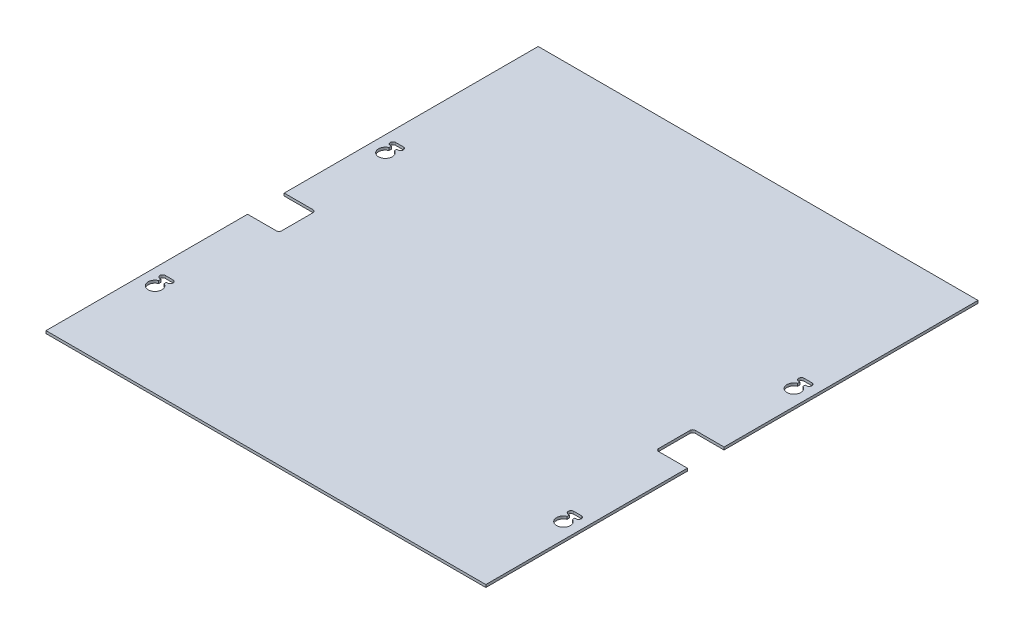
SolidWorks part; units mm, degrees
material "PC High Viscosity"
ref_plane "Front Plane" through (0, 0, 0) normal (0, 0, 1) x (1, 0, 0)
ref_plane "Top Plane" through (0, 0, 0) normal (0, 1, 0) x (1, 0, 0)
ref_plane "Right Plane" through (0, 0, 0) normal (1, 0, 0) x (0, 0, -1)
sketch "Sketch1" plane through (0, 0, 0) normal (0, 1, 0) x (1, 0, 0)
  line L1 (-266.7, -298.45) -> (266.7, -298.45)
  line L2 (-266.7, -298.45) -> (-266.7, 298.45)
  line L3 (-266.7, 298.45) -> (266.7, 298.45)
  line L4 (266.7, -298.45) -> (266.7, 298.45)
  line L5 (-266.7, -298.45) -> (266.7, 298.45) construction
  line L6 (-266.7, 298.45) -> (266.7, -298.45) construction
  point P0 (0, 0)
  dimension "D1" = 533.4
  dimension "D2" = 596.9
extrude "Boss-Extrude1" add sketch "Sketch1" along normal blind 3.175
sketch "Sketch5" plane through (0, 0, 0) normal (0, -1, 0) x (1, 0, 0)
  line L0 (247.65, -111.2139) -> (247.65, -85.7758) construction
  line L1 (244.3858, -101.8782) -> (244.3858, -107.9506)
  line L2 (247.65, 168.1861) -> (247.65, 193.6242) construction
  line L3 (250.9136, -101.8783) -> (250.9136, -107.95)
  line L4 (0, -298.45) -> (0, 298.45) construction
  line L5 (266.7, -298.45) -> (-266.7, -298.45) construction
  line L6 (-266.7, 298.45) -> (266.7, 298.45) construction
  line L13 (250.9139, 177.5218) -> (250.9139, 171.45)
  line L15 (244.3861, 177.5218) -> (244.3861, 171.45)
  line L16 (-247.65, 168.1861) -> (-247.65, 193.6242) construction
  line L17 (-247.65, -111.2139) -> (-247.65, -85.7758) construction
  line L18 (-244.3861, 177.5218) -> (-244.3861, 171.45)
  line L19 (-250.9139, 177.5218) -> (-250.9139, 171.45)
  line L20 (-250.9136, -101.8783) -> (-250.9136, -107.95)
  line L21 (-244.3858, -101.8782) -> (-244.3858, -107.9506)
  line L22 (247.65, 298.45) -> (247.65, -298.45) construction
  line L23 (-266.7, 298.45) -> (266.7, 298.45) construction
  line L24 (266.7, -298.45) -> (-266.7, -298.45) construction
  arc A0 (-244.3861, 171.45) -> (-250.9139, 171.45) centre (-247.65, 171.45) cw
  arc A1 (-250.9139, 177.5218) -> (-244.3861, 177.5218) centre (-247.65, 185.2422) cw
  arc A2 (250.9136, -101.8783) -> (244.3858, -101.8782) centre (247.6498, -94.1578) ccw
  arc A3 (-244.3858, -107.9506) -> (-250.9136, -107.95) centre (-247.6497, -107.95) cw
  arc A4 (244.3858, -107.9506) -> (250.9136, -107.95) centre (247.6497, -107.95) ccw
  arc A5 (-250.9136, -101.8783) -> (-244.3858, -101.8782) centre (-247.6498, -94.1578) cw
  arc A6 (250.9139, 177.5218) -> (244.3861, 177.5218) centre (247.65, 185.2422) ccw
  arc A8 (244.3861, 171.45) -> (250.9139, 171.45) centre (247.65, 171.45) ccw
  dimension "D1" = 8.382
  dimension "D2" = 113.2078
  dimension "D4" = 247.65
  dimension "D5" = 6.5278
  dimension "D7" = 3.2639
  dimension "D3" = 25.4381
  dimension "D6" = 190.5
  dimension "D8" = 6.5278
  dimension "D9" = 9.3357
  dimension "D10" = 9.3357
extrude "Cut-Extrude1" cut sketch "Sketch5" against normal through all
hole_wizard "F (0.257) Diameter Slot1" positions "Sketch6" profile "Sketch7" size "F" standard "ANSI Inch" slot yes end condition through all
sketch "Sketch6" plane through (0, 0, 0) normal (0, -1, 0) x (-1, 0, 0)
  line L0 (255.5875, -168.1861) -> (239.7125, -168.1861) construction
  line L1 (255.5875, -171.45) -> (239.7125, -171.45) construction
  point P7 (247.65, -171.45)
  point P12 (247.6497, 107.95)
  point P15 (-247.6497, 107.95)
  point P18 (-247.65, -171.45)
  dimension "D1" = 15.875
  dimension "D2" = 15.875
sketch "Sketch7" plane through (247.65, 0, 171.45) normal (1, 0, 0) x (0, 0, -1)
  line L0 (0, 0) -> (0, 3.175)
  line L1 (0, 3.175) -> (3.2639, 3.175)
  line L2 (3.2639, 3.175) -> (3.2639, 0)
  line L5 (3.2639, 0) -> (0, 0)
  line L11 (0, -6.35) -> (0, 107.95) construction
  dimension "Thru Hole Dia." = 6.5278
  dimension "Thru Hole Depth" = 3.175
sketch "Sketch8" plane through (0, 0, 0) normal (0, -1, 0) x (1, 0, 0)
  line L1 (0, 298.45) -> (0, -298.45) construction
  line L2 (-266.7, -298.45) -> (-266.7, 298.45) construction
  line L3 (-228.6, 53.975) -> (-266.7, 53.975)
  line L4 (-228.6, 53.975) -> (-228.6, 9.525)
  line L5 (-228.6, 9.525) -> (-266.7, 9.525)
  line L6 (-266.7, 53.975) -> (-266.7, 9.525)
  line L7 (-228.6, 53.975) -> (-266.7, 9.525) construction
  line L8 (-228.6, 9.525) -> (-266.7, 53.975) construction
  line L14 (-266.7, 298.45) -> (266.7, 298.45) construction
  line L15 (228.6, 9.525) -> (266.7, 53.975) construction
  line L16 (228.6, 53.975) -> (266.7, 9.525) construction
  line L17 (254.0001, 171.45) -> (252.4122, -107.95) construction
  line L18 (266.7, 53.975) -> (266.7, 9.525)
  line L19 (228.6, 9.525) -> (266.7, 9.525)
  line L20 (228.6, 53.975) -> (228.6, 9.525)
  line L21 (228.6, 53.975) -> (266.7, 53.975)
  point P10 (-247.65, 31.75)
  point P12 (-247.65, 31.75)
  point P26 (247.65, 31.75)
  dimension "D1" = 44.45
  dimension "D2" = 38.1
  dimension "D3" = 266.7
extrude "Cut-Extrude2" cut sketch "Sketch8" against normal through all
fillet "Fillet1" radius 3.175 4 edges at (-228.6, 1.5875, 53.975) (-228.6, 1.5875, 9.525) (228.6, 1.5875, 53.975) (228.6, 1.5875, 9.525)
